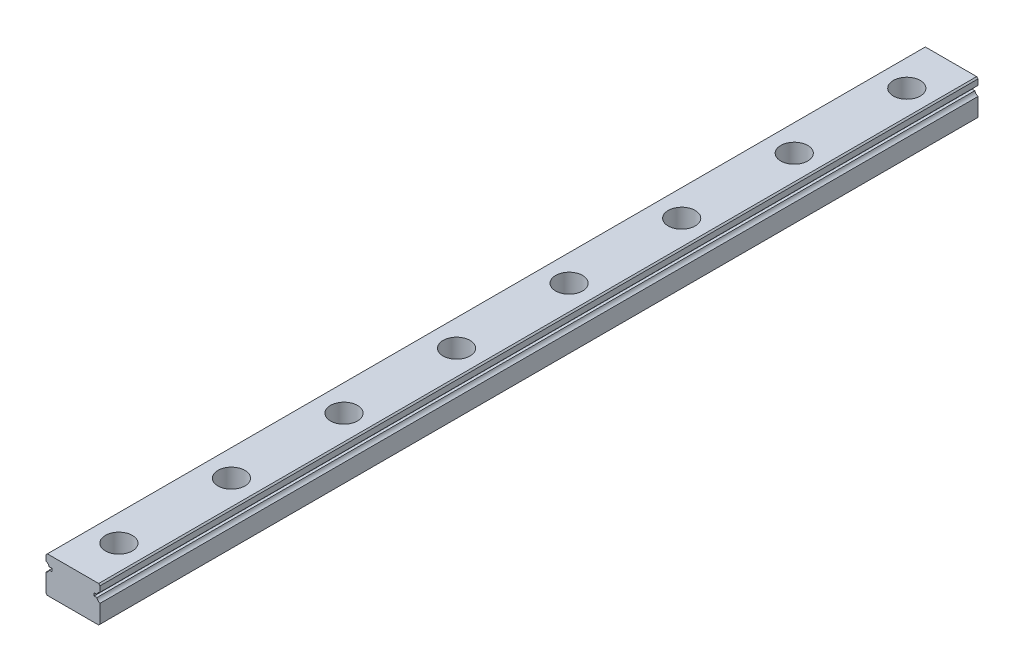
SolidWorks part; units mm, degrees
ref_plane "Спереди" through (0, 0, 0) normal (0, 0, 1) x (1, 0, 0)
ref_plane "Сверху" through (0, 0, 0) normal (0, 1, 0) x (1, 0, 0)
ref_plane "Справа" through (0, 0, 0) normal (1, 0, 0) x (0, 0, -1)
sketch "Эскиз1" plane through (0, 0, 0) normal (0, 0, 1) x (1, 0, 0)
  line L0 (-6, 3.7) -> (-5.7, 4)
  line L1 (-5.7, -4) -> (5.7, -4)
  line L2 (-6, -3.7) -> (-6, 0.3334)
  line L3 (-5.7, 4) -> (5.7, 4)
  line L4 (6, -3.7) -> (6, 0.3334)
  line L5 (-6, -4) -> (6, 4) construction
  line L6 (-6, 4) -> (6, -4) construction
  line L7 (-6, -3.7) -> (-5.7, -4)
  line L8 (5.7, -4) -> (6, -3.7)
  line L9 (5.7, 4) -> (6, 3.7)
  line L10 (-6, 2.4498) -> (-6, 3.7)
  line L11 (-5.2979, 1.7203) -> (-4.6875, 1.7203)
  line L12 (0, 5.4188) -> (0, -5.747) construction
  line L13 (-5.2922, 1.0823) -> (-4.6875, 1.0823)
  line L14 (-4.6875, 1.7203) -> (-4.6875, 1.0823)
  line L15 (4.6875, 1.7203) -> (4.6875, 1.0823)
  line L16 (5.2922, 1.0823) -> (4.6875, 1.0823)
  line L17 (5.2979, 1.7203) -> (4.6875, 1.7203)
  line L18 (6, 2.4498) -> (6, 3.7)
  arc A0 (-6, 0.3334) -> (-5.2922, 1.0823) centre (-6.3695, 1.3916) ccw
  arc A1 (-5.2979, 1.7203) -> (-6, 2.4498) centre (-6.3695, 1.3916) ccw
  arc A2 (5.2979, 1.7203) -> (6, 2.4498) centre (6.3695, 1.3916) cw
  arc A3 (6, 0.3334) -> (5.2922, 1.0823) centre (6.3695, 1.3916) cw
  point P0 (0, 0)
extrude "Бобышка-Вытянуть1" add sketch "Эскиз1" along normal blind 195
sketch "Эскиз2" plane through (0, 4, 0) normal (0, 1, 0) x (1, 0, 0)
  line L0 (0, 0) -> (0, -26.2396) construction
  line L1 (5.7, 0) -> (-5.7, 0) construction
  line L2 (-3.8306, -10) -> (4.207, -10) construction
  circle A0 centre (0.1882, -10) radius 3
  circle A1 centre (0.1882, -10) radius 1.75
  dimension "D1" = 10
extrude "Вырез-Вытянуть1" cut sketch "Эскиз2" against normal blind 4.5
extrude "Вырез-Вытянуть2" cut sketch "Эскиз2<2>" against normal through all contours A1 region at (0.1882, 4, 10)
sketch "Эскиз2<2>" plane through (0, 4, 0) normal (0, 1, 0) x (1, 0, 0) same geometry as "Эскиз2"
pattern_linear "Линейный массив1" count 12 spacing 25 along (0, 0, 1) of "Вырез-Вытянуть1", "Вырез-Вытянуть2"
